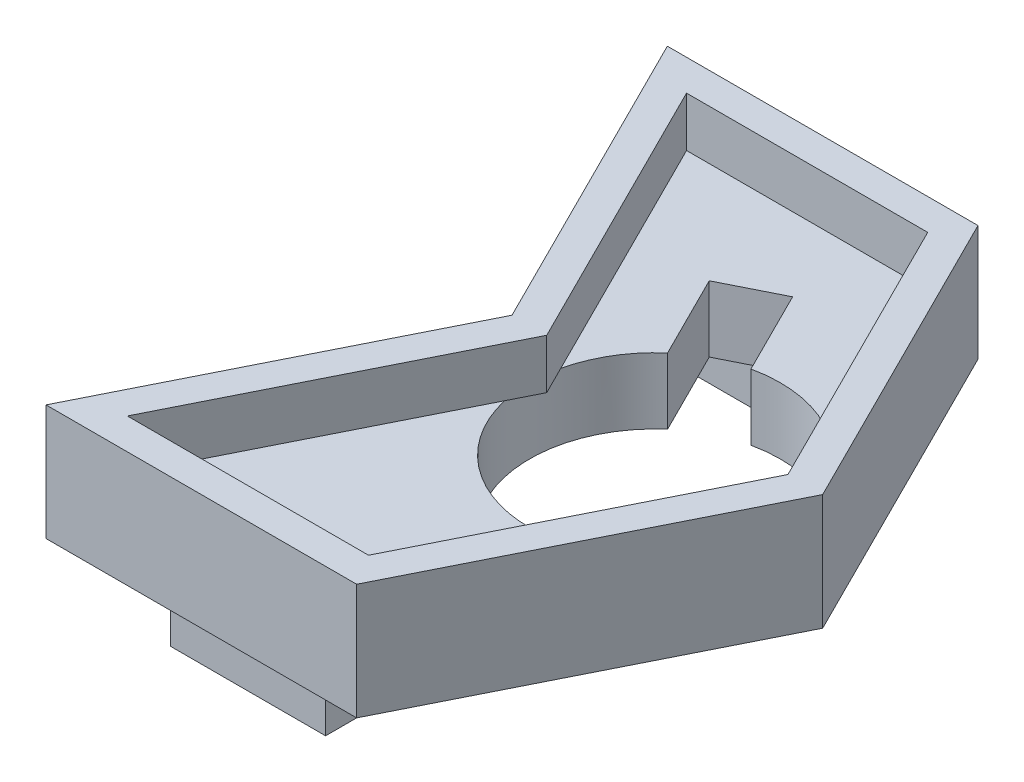
SolidWorks part; units mm, degrees
ref_plane "Front Plane" through (0, 0, 0) normal (0, 0, 1) x (1, 0, 0)
ref_plane "Top Plane" through (0, 0, 0) normal (0, 1, 0) x (1, 0, 0)
ref_plane "Right Plane" through (0, 0, 0) normal (1, 0, 0) x (0, 0, -1)
sketch "Sketch1" plane through (0, 0, 0) normal (0, 1, 0) x (1, 0, 0)
  line L0 (0, 0) -> (12.7, 0)
  line L1 (12.7, 0) -> (19.05, 12.7)
  line L2 (19.05, 12.7) -> (12.7, 25.4)
  line L3 (12.7, 25.4) -> (0, 25.4)
  line L4 (0, 25.4) -> (6.35, 12.7)
  line L5 (6.35, 12.7) -> (0, 0)
  dimension "D1" = 12.7
  dimension "D2" = 25.4
  dimension "D3" = 6.35
  dimension "D5" = 12.7
extrude "Boss-Extrude1" add sketch "Sketch1" along normal blind 6.35
sketch "Sketch2" plane through (0, 0, 0) normal (0, -1, 0) x (1, 0, 0)
  line L0 (19.05, -12.7) -> (6.35, -12.7) construction
  line L1 (6.35, -12.7) -> (0, 0) construction
  circle A0 centre (12.192, -12.7) radius 5.127
  dimension "D1" = 10.254
  dimension "D2" = 5.842
extrude "Cut-Extrude1" cut sketch "Sketch2" against normal blind 2.7 contours A0
sketch "Sketch3" plane through (0, 0, 0) normal (0, -1, 0) x (1, 0, 0)
  line L8 (11.1065, -17.7108) -> (8.8347, -16.5749)
  line L9 (11.1065, -17.7108) -> (9.4026, -21.1185)
  line L10 (8.8347, -16.5749) -> (7.1308, -19.9826)
  line L11 (9.4026, -21.1185) -> (7.1308, -19.9826)
  line L12 (19.05, -12.7) -> (12.7, -25.4) construction
  circle A3 centre (12.192, -12.7) radius 5.127 construction
  dimension "D1" = 2.54
  dimension "D2" = 3.81
extrude "Cut-Extrude2" cut sketch "Sketch3" against normal blind 2.7
ref_plane "MidPlane" through (0, 0, -12.7) normal (0, 0, -1) x (-1, 0, 0)
sketch "Sketch4" plane through (0, 0, 0) normal (0, -1, 0) x (1, 0, 0)
  line L0 (12.7, -25.4) -> (0, -25.4) construction
  line L1 (10.16, -24.13) -> (3.81, -24.13)
  line L2 (10.16, -24.13) -> (10.16, -21.59)
  line L3 (10.16, -21.59) -> (3.81, -21.59)
  line L4 (3.81, -24.13) -> (3.81, -21.59)
  line L5 (0, -55) -> (0, 55) construction
  dimension "D1" = 2.54
  dimension "D2" = 6.35
  dimension "D3" = 1.27
  dimension "D4" = 3.81
extrude "Boss-Extrude2" add sketch "Sketch4" along normal blind 2.54
mirror "Mirror1" about plane through (0, 0, -12.7) normal (0, 0, -1) of "Boss-Extrude2"
ref_point "Point1"
ref_axis "Axis1" through (0, 6.35, -25.4) along (0, 0, 1)
sketch "Sketch5" plane through (0, 6.35, 0) normal (0, 1, 0) x (1, 0, 0)
  line L0 (0, 25.4) -> (0, 0) construction
  line L1 (0, 12.7) -> (19.05, 12.7) construction
sketch "Sketch6" plane through (0, 6.35, 0) normal (0, 1, 0) x (1, 0, 0)
  line L0 (2.0549, 24.13) -> (11.9151, 24.13)
  line L1 (11.9151, 24.13) -> (17.6301, 12.7)
  line L2 (0, 12.7) -> (19.05, 12.7) construction
  line L3 (17.6301, 12.7) -> (11.9151, 1.27)
  line L4 (11.9151, 1.27) -> (2.0549, 1.27)
  line L5 (2.0549, 1.27) -> (7.7699, 12.7)
  line L6 (7.7699, 12.7) -> (2.0549, 24.13)
  line L7 (12.7, 25.4) -> (0, 25.4) construction
  line L8 (-4.8895, 0) -> (4.8895, 0) construction
  line L9 (6.35, 12.7) -> (0, 0) construction
  line L10 (12.7, 0) -> (19.05, 12.7) construction
  line L11 (0, 25.4) -> (6.35, 12.7) construction
  line L12 (19.05, 12.7) -> (12.7, 25.4) construction
  dimension "D1" = 1.27
  dimension "D2" = 1.27
  dimension "D3" = 1.27
  dimension "D4" = 1.27
extrude "Cut-Extrude3" cut sketch "Sketch6" along direction (0, -1, 0) on the side against the normal up to surface (3.65 mm away) up to face at (10.2472, 2.7, -16.5896)
sketch "Sketch7" plane through (0, 6.35, 0) normal (0, 1, 0) x (1, 0, 0)
  line L1 (23.79, -1.3137) -> (-3.8509, -1.3137)
  line L2 (23.79, -1.3137) -> (23.79, 27.4869)
  line L3 (23.79, 27.4869) -> (-3.8509, 27.4869)
  line L4 (-3.8509, -1.3137) -> (-3.8509, 27.4869)
extrude "Cut-Extrude4" cut sketch "Sketch7" against normal blind 1.618
equation "\"Arrow Height\"= 1in"
equation "\"Button Height\"= 2in"
equation "\"Button Width\"= 4in"
equation "\"Haptic Diameter\"= 10mm"
equation "\"Haptic Thickness\"= 2.7mm"
equation "\"D2@Sketch1\"=\"Arrow Height\""
equation "\"D5@Sketch1\"=\"Arrow Height\"/2"
equation "\"D1@Sketch2\"=\"Haptic Diameter\"+.01in"
equation "\"D1@Cut-Extrude1\"=\"Haptic Thickness\""
equation "\"D1@Cut-Extrude2\"=\"Haptic Thickness\""
equation "\"Arrow Spacing\"= 1in"
equation "\"Arrow Width\"= 0.75in"
equation "\"Haptic Wire Angle\"= 63.43"
equation "\"Haptic Wire Width\"= .1in"
equation "\"Haptic Wire Height\"= .15in"
